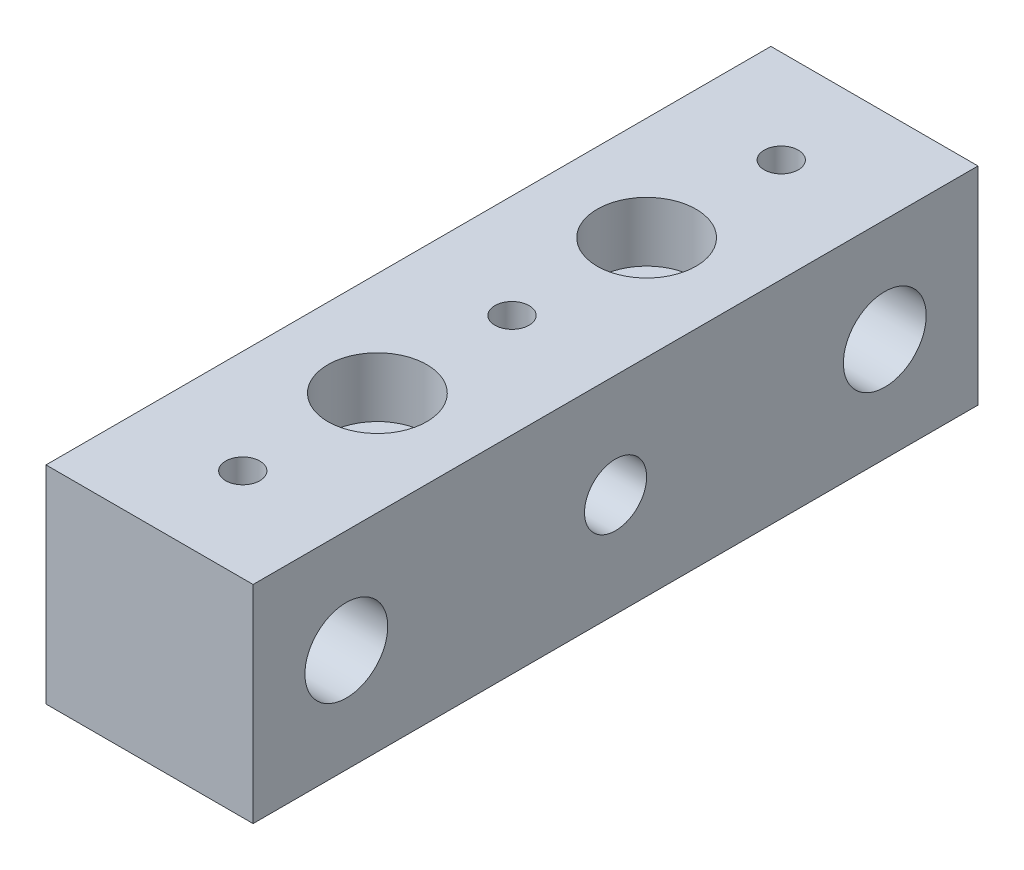
SolidWorks part; units mm, degrees
ref_plane "Plano frontal" through (0, 0, 0) normal (0, 0, 1) x (1, 0, 0)
ref_plane "Plano superior" through (0, 0, 0) normal (0, 1, 0) x (1, 0, 0)
ref_plane "Plano direito" through (0, 0, 0) normal (1, 0, 0) x (0, 0, -1)
sketch "Esboço1" plane through (0, 0, 0) normal (0, 1, 0) x (1, 0, 0)
  line L1 (-10, -35) -> (10, -35)
  line L2 (-10, -35) -> (-10, 35)
  line L3 (-10, 35) -> (10, 35)
  line L4 (10, -35) -> (10, 35)
  line L5 (-10, -35) -> (10, 35) construction
  line L6 (-10, 35) -> (10, -35) construction
  point P0 (0, 0)
  dimension "D1" = 20
  dimension "D2" = 70
base flange "Flange-base1" sketch "Esboço1" thickness 20 reverse thickness direction no parameters "D1"=10
sketch "Esboço3" plane through (0, 0, 0) normal (0, 1, 0) x (1, 0, 0)
  line L0 (0, -13) -> (0, 13) construction
  circle A0 centre (0, 13) radius 4.775
  circle A1 centre (0, -13) radius 4.775
  point P4 (0, 0)
extrude "Corte-extrusão1" cut sketch "Esboço3" against normal blind 5.75 normal cut yes
sketch "Esboço4" plane through (0, -5.75, 0) normal (0, 1, 0) x (1, 0, 0)
  circle A0 centre (0, 13) radius 2.65
  circle A1 centre (0, -13) radius 2.65
extrude "Corte-extrusão2" cut sketch "Esboço4" against normal through all normal cut yes
sketch "Esboço5" plane through (10, 0, 0) normal (1, 0, 0) x (0, 0, -1)
  line L0 (-35, -10) -> (-30, -10) construction
  line L4 (-35, -20) -> (-35, 0) construction
  line L5 (-30, -10) -> (-26, -10) construction
  line L6 (35, -10) -> (30, -10) construction
  line L7 (35, -20) -> (35, 0) construction
  line L8 (30, -10) -> (26, -10) construction
  line L9 (0, 0) -> (0, -20) construction
  line L10 (-35, -20) -> (35, -20) construction
  circle A0 centre (-26, -10) radius 4
  circle A1 centre (26, -10) radius 4
  circle A2 centre (0, -10) radius 3
extrude "Corte-extrusão3" cut sketch "Esboço5" against normal through all normal cut yes
sketch "Esboço6" plane through (0, 0, 0) normal (0, 1, 0) x (1, 0, 0)
  line L0 (0, -22) -> (0, -30) construction
  line L1 (10, -22) -> (-10, -22) construction
  line L2 (-10, -30) -> (10, -30) construction
  line L3 (0, 30) -> (0, 22) construction
  line L4 (10, 30) -> (-10, 30) construction
  line L5 (-10, 22) -> (10, 22) construction
  line L6 (0, 3) -> (0, -3) construction
  line L7 (10, 3) -> (-10, 3) construction
  line L8 (-10, -3) -> (10, -3) construction
  circle A0 centre (0, -26) radius 1.65
  circle A1 centre (0, 26) radius 1.65
  circle A2 centre (0, 0) radius 1.65
extrude "Corte-extrusão5" cut sketch "Esboço6" against normal up to next normal cut yes
sketch "Curva-Linhas1" [suppressed] plane through (0, 0, 0) normal (0, 1, 0) x (1, 0, 0)
sketch "Caixa delimitadora1" [suppressed] plane through (0, 0, 0) normal (0, 1, 0) x (1, 0, 0)
sheet metal parameters "Chapa metálica1" thickness 20 parameters "D1"=10
flat pattern "Padrão-Plano1" [suppressed]
sketch "Curva-Linhas2" plane through (0, 0, 0) normal (0, 1, 0) x (1, 0, 0)
sketch3d "Caixa delimitadora2" [suppressed]
  line L0 (-10, -35, 0) -> (-10, 35, 0) construction
  line L1 (10, -35, 0) -> (10, 35, 0) construction
  line L2 (-10, -35, 0) -> (10, -35, 0) construction
  line L3 (-10, 35, 0) -> (10, 35, 0) construction
sheet metal parameters "Chapa metálica2" thickness 20 parameters "D1"=10
flat pattern "Padrão-Plano1"
sketch "Curva-Linhas2" plane through (0, 0, 0) normal (0, 1, 0) x (1, 0, 0)
sketch3d "Caixa delimitadora2" [suppressed]
  line L0 (-10, -35, 0) -> (-10, 35, 0) construction
  line L1 (10, -35, 0) -> (10, 35, 0) construction
  line L2 (-10, -35, 0) -> (10, -35, 0) construction
  line L3 (-10, 35, 0) -> (10, 35, 0) construction
sheet metal parameters "Chapa metálica3" thickness 20 parameters "D1"=10
flat pattern "Padrão-Plano1"
sketch "Curva-Linhas2" plane through (0, 0, 0) normal (0, 1, 0) x (1, 0, 0)
sketch3d "Caixa delimitadora2" [suppressed]
  line L0 (-10, -35, 0) -> (-10, 35, 0) construction
  line L1 (10, -35, 0) -> (10, 35, 0) construction
  line L2 (-10, -35, 0) -> (10, -35, 0) construction
  line L3 (-10, 35, 0) -> (10, 35, 0) construction
sheet metal parameters "Chapa metálica4" thickness 20 parameters "D1"=10
flat pattern "Padrão-Plano1"
sketch "Curva-Linhas2" plane through (0, 0, 0) normal (0, 1, 0) x (1, 0, 0)
sketch3d "Caixa delimitadora2" [suppressed]
  line L0 (-10, -35, 0) -> (-10, 35, 0) construction
  line L1 (10, -35, 0) -> (10, 35, 0) construction
  line L2 (-10, -35, 0) -> (10, -35, 0) construction
  line L3 (-10, 35, 0) -> (10, 35, 0) construction
sheet metal parameters "Chapa metálica6" thickness 20 parameters "D1"=10
flat pattern "Padrão-Plano1"
sketch "Curva-Linhas2" plane through (0, 0, 0) normal (0, 1, 0) x (1, 0, 0)
sketch3d "Caixa delimitadora2" [suppressed]
  line L0 (-10, -35, 0) -> (-10, 35, 0) construction
  line L1 (10, -35, 0) -> (10, 35, 0) construction
  line L2 (-10, -35, 0) -> (10, -35, 0) construction
  line L3 (-10, 35, 0) -> (10, 35, 0) construction
